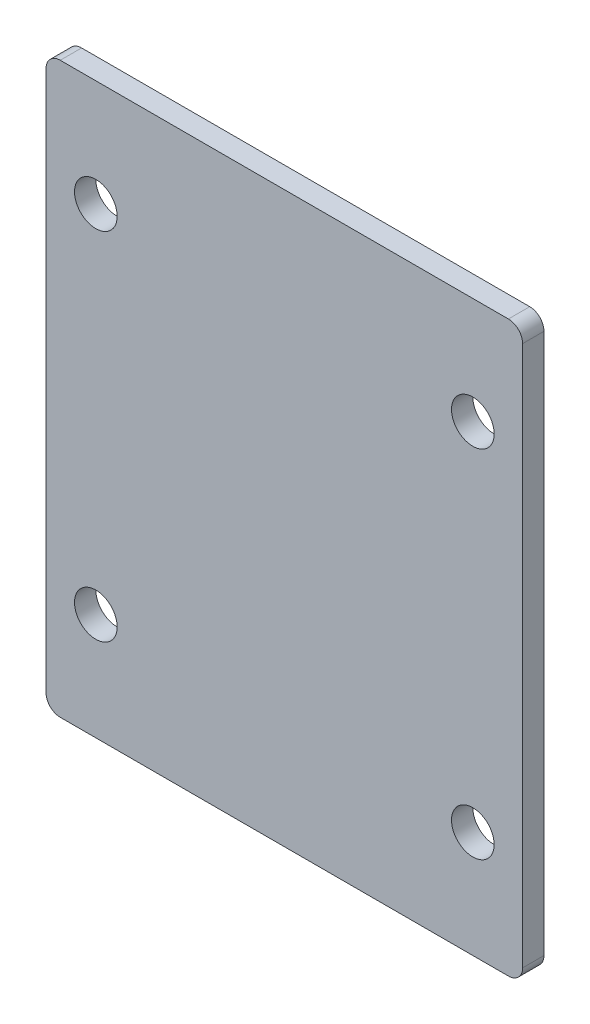
SolidWorks part; units mm, degrees
ref_plane "Front Plane" through (0, 0, 0) normal (0, 0, 1) x (1, 0, 0)
ref_plane "Top Plane" through (0, 0, 0) normal (0, 1, 0) x (1, 0, 0)
ref_plane "Right Plane" through (0, 0, 0) normal (1, 0, 0) x (0, 0, -1)
sketch "Sketch2" plane through (0, 0, 0) normal (0, 0, 1) x (1, 0, 0)
  line L2 (258.5799, 180.7072) -> (292.0799, 180.7072)
  line L3 (258.5799, 180.7072) -> (258.5799, 220.7072)
  line L4 (258.5799, 220.7072) -> (292.0799, 220.7072)
  line L5 (292.0799, 180.7072) -> (292.0799, 220.7072)
  circle A0 centre (288.5799, 213.2072) radius 1.5
  circle A1 centre (288.5799, 188.2072) radius 1.5
  circle A2 centre (262.0799, 213.2072) radius 1.5
  circle A3 centre (262.0799, 188.2072) radius 1.5
  point P6 (0, 0)
  dimension "D1" = 33.5
  dimension "D2" = 40
  dimension "D4" = 3.5
  dimension "D6" = 26.5
  dimension "D7" = 3.5
  dimension "D8" = 7.5
  dimension "D3" = 2
  dimension "D5" = 2
base flange "Base-Flange1" sketch "Sketch2" thickness 1.5 reverse thickness direction no parameters "D1"=0.7366
fillet "Fillet1" radius 1 4 edges at (292.0799, 180.7072, -0.75) (292.0799, 220.7072, -0.75) (258.5799, 220.7072, -0.75) (258.5799, 180.7072, -0.75)
sketch "Bend-Lines1" [suppressed] plane through (0, 0, 0) normal (0, 1, 0) x (1, 0, 0)
sketch "Bounding-Box1" [suppressed] plane through (0, 0, 0) normal (0, 1, 0) x (1, 0, 0)
sheet metal parameters "Sheet-Metal1" thickness 1.5 parameters "D1"=0.7366
flat pattern "Flat-Pattern1" [suppressed]
sketch "Bend-Lines2" plane through (0, 0, 0) normal (0, 1, 0) x (1, 0, 0)
sketch3d "Bounding-Box2" [suppressed]
  line L0 (292.0799, 220.7072, 0) -> (292.0799, 180.7072, 0) construction
  line L1 (258.5799, 220.7072, 0) -> (258.5799, 180.7072, 0) construction
  line L2 (292.0799, 220.7072, 0) -> (258.5799, 220.7072, 0) construction
  line L3 (292.0799, 180.7072, 0) -> (258.5799, 180.7072, 0) construction
